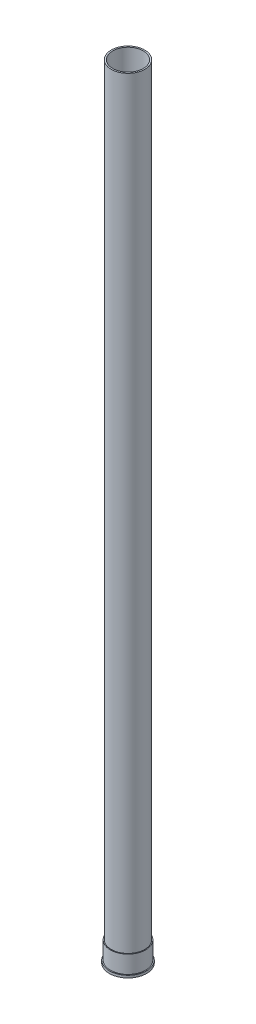
SolidWorks part; units mm, degrees
ref_plane "Front Plane" through (0, 0, 0) normal (0, 0, 1) x (1, 0, 0)
ref_plane "Top Plane" through (0, 0, 0) normal (0, 1, 0) x (1, 0, 0)
ref_plane "Right Plane" through (0, 0, 0) normal (1, 0, 0) x (0, 0, -1)
sketch "Sketch1" plane through (0, 0, 0) normal (0, 1, 0) x (1, 0, 0)
  circle A0 centre (0, 0) radius 15
  circle A1 centre (0, 0) radius 13.462
  circle A2 centre (0, 0) radius 15.875
  dimension "D1" = 30
  dimension "D2" = 31.75
  dimension "D3" = 2.413
extrude "Boss-Extrude1" add sketch "Sketch1" along normal blind 15 contours A0 A1 region at (-14.5757, 0, 0)
sketch "Sketch4" plane through (0, 15, 0) normal (0, 1, 0) x (1, 0, 0)
  circle A0 centre (0, 0) radius 14.2875
  circle A2 centre (0, 0) radius 13.0429
  circle M3 centre (0, 0) radius 13.462
  dimension "D1" = 28.575
  dimension "D2" = 1.2446
extrude "Boss-Extrude5" add sketch "Sketch4" along normal blind 650 contours A2 M3 | A0 M3 region at (-13.8834, 15, 0) region at (-13.0812, 15, 0)
extrude "Boss-Extrude6" add sketch "Sketch1<4>" against normal blind 2 contours A2 A0 | A0 A1 region at (-14.5757, 0, 0) region at (-15.426, 0, 0)
sketch "Sketch1<4>" plane through (0, 0, 0) normal (0, 1, 0) x (1, 0, 0) same geometry as "Sketch1"
equation "\"bottomheight\"= 15"
equation "\"D1@Boss-Extrude1\"=\"bottomheight\""
equation "\"topheight\"= 650"
equation "\"D1@Boss-Extrude5\"=\"topheight\""
equation "\"spacerheight\"=2"
equation "\"D1@Boss-Extrude6\"=\"spacerheight\""
